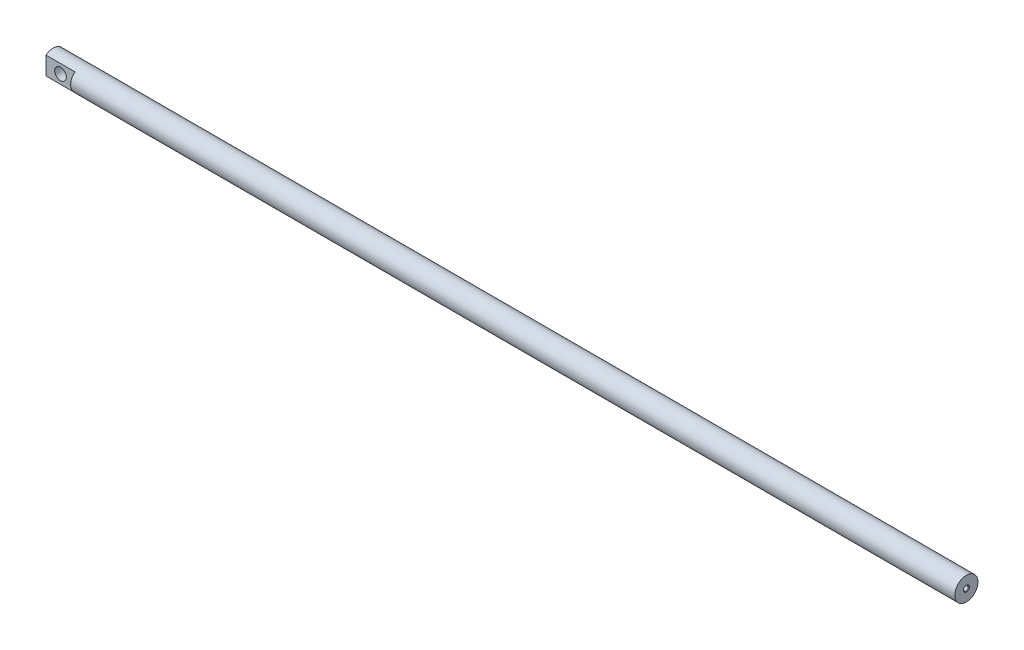
SolidWorks part; units mm, degrees
ref_plane "前视基准面" through (0, 0, 0) normal (0, 0, 1) x (1, 0, 0)
ref_plane "上视基准面" through (0, 0, 0) normal (0, 1, 0) x (1, 0, 0)
ref_plane "右视基准面" through (0, 0, 0) normal (1, 0, 0) x (0, 0, -1)
sketch "草图1" plane through (0, 0, 0) normal (1, 0, 0) x (0, 0, -1)
  circle A0 centre (0, 0) radius 8
  dimension "D1" = 16
extrude "凸台-拉伸1" add sketch "草图1" along normal blind 630
sketch "草图3" plane through (0, 0, 0) normal (-1, 0, 0) x (0, 0, 1)
  line L1 (-5, 10) -> (5, 10)
  line L2 (-5, 10) -> (-5, -10)
  line L3 (-5, -10) -> (5, -10)
  line L4 (5, 10) -> (5, -10)
  line L5 (-5, 10) -> (5, -10) construction
  line L6 (-5, -10) -> (5, 10) construction
  point P0 (0, 0)
  dimension "D1" = 20
  dimension "D2" = 10
extrude "切除-拉伸1" cut sketch "草图3" against normal blind 20 flip side to cut
sketch "草图4" plane through (0, 0, -5) normal (0, 0, -1) x (-1, 0, 0)
  line L0 (0, 6.245) -> (-20, 6.245) construction
  circle A0 centre (-10, 0) radius 4
  point P6 (-10, 6.245)
  dimension "D1" = 8
extrude "切除-拉伸3" cut sketch "草图4" against normal blind 20
sketch "草图5" plane through (630, 0, 0) normal (1, 0, 0) x (0, 0, -1)
  circle A0 centre (0, 0) radius 2 construction
  dimension "D1" = 4
hole_wizard "M4 螺纹孔1" positions "3D草图1" profile "草图6" tap size "M4" standard "GB"
sketch3d "3D草图1"
  point P0 (630, 0, 0)
sketch "草图6" plane through (630, 0, 0) normal (0, 1, 0) x (0, 0, -1)
  line L0 (0, 0) -> (0, 10.9914)
  line L1 (0, 10.9914) -> (1.65, 10)
  line L2 (1.65, 10) -> (1.65, 0.375)
  line L3 (1.65, 0.375) -> (2.025, 0)
  line L5 (2.025, 0) -> (0, 0)
  line L6 (-1.65, 0.375) -> (-2.025, 0) construction
  line L10 (0, 10.9914) -> (-1.65, 10) construction
  line L11 (0, -6.35) -> (0, 107.95) construction
  dimension "螺纹孔钻头直径" = 3.3
  dimension "螺纹孔钻头深度" = 10
  dimension "近端锥形沉头孔直径" = 4.05
  dimension "近端锥形沉头孔角度" = 90
  dimension "导头角度" = 118
cosmetic thread "孔螺蚊线1" parameters "D1"=9, "D2"=4
